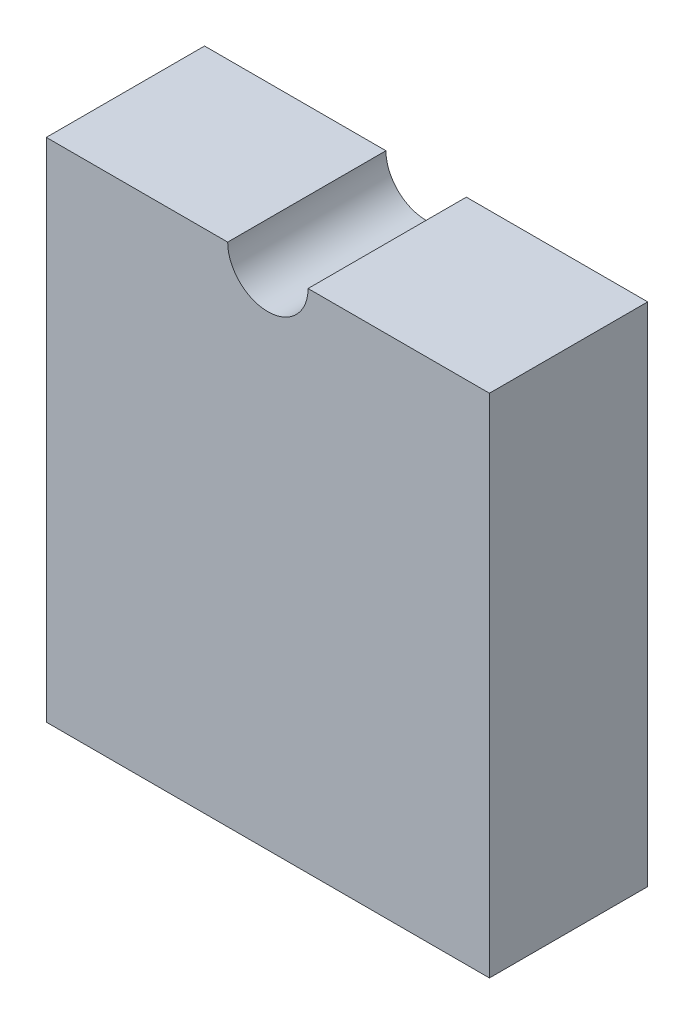
SolidWorks part; units mm, degrees
ref_plane "Front Plane" through (0, 0, 0) normal (0, 0, 1) x (1, 0, 0)
ref_plane "Top Plane" through (0, 0, 0) normal (0, 1, 0) x (1, 0, 0)
ref_plane "Right Plane" through (0, 0, 0) normal (1, 0, 0) x (0, 0, -1)
sketch "Sketch2" plane through (0, 0, 0) normal (0, 1, 0) x (1, 0, 0)
  line L0 (-35, 0) -> (35, 0)
  line L2 (-35, 0) -> (-35, -25)
  line L3 (-35, -25) -> (35, -25)
  line L4 (35, 0) -> (35, -25)
  line L5 (0, 0) -> (35, -25) construction
  line L6 (-35, -25) -> (0, 0) construction
  line L7 (-35, 20.0732) -> (-35, 0) construction
  line L8 (35, 20.0732) -> (35, 0) construction
  line L9 (-35, 20.0732) -> (35, 20.0732) construction
  arc A0 (-15, 0) -> (15, 0) centre (0, 0) ccw
  point P0 (0, 0)
  point P9 (0, 0)
  dimension "D1" = 30
  dimension "D2" = 25
  dimension "D3" = 35
extrude "Boss-Extrude2" add sketch "Sketch2" against normal blind 50 separate body contours A0 L0 L2 L3 L4 region at (-25, 0, 0.7433)
sketch "Sketch3" plane through (0, 0, 25) normal (0, 0, 1) x (1, 0, 0)
  line L0 (-35, 0) -> (-35, 30)
  line L1 (-35, 30) -> (35, 30)
  line L2 (35, 30) -> (35, 0)
  line L3 (35, 0) -> (-35, 0)
  line L4 (35, -50) -> (35, 0) construction
  line L5 (-35, -50) -> (-35, 0) construction
  arc A0 (-6.35, 30) -> (6.35, 30) centre (0, 30) ccw
  line M6 (35, 0) -> (-35, 0)
  dimension "D1" = 12.7
  dimension "D2" = 30
extrude "Boss-Extrude3" add sketch "Sketch3" against normal up to surface (25 mm away) contours A0 L1 L0 L2 M6 region at (0, 14.6173, 25) up to face at (25, -25, 0)
